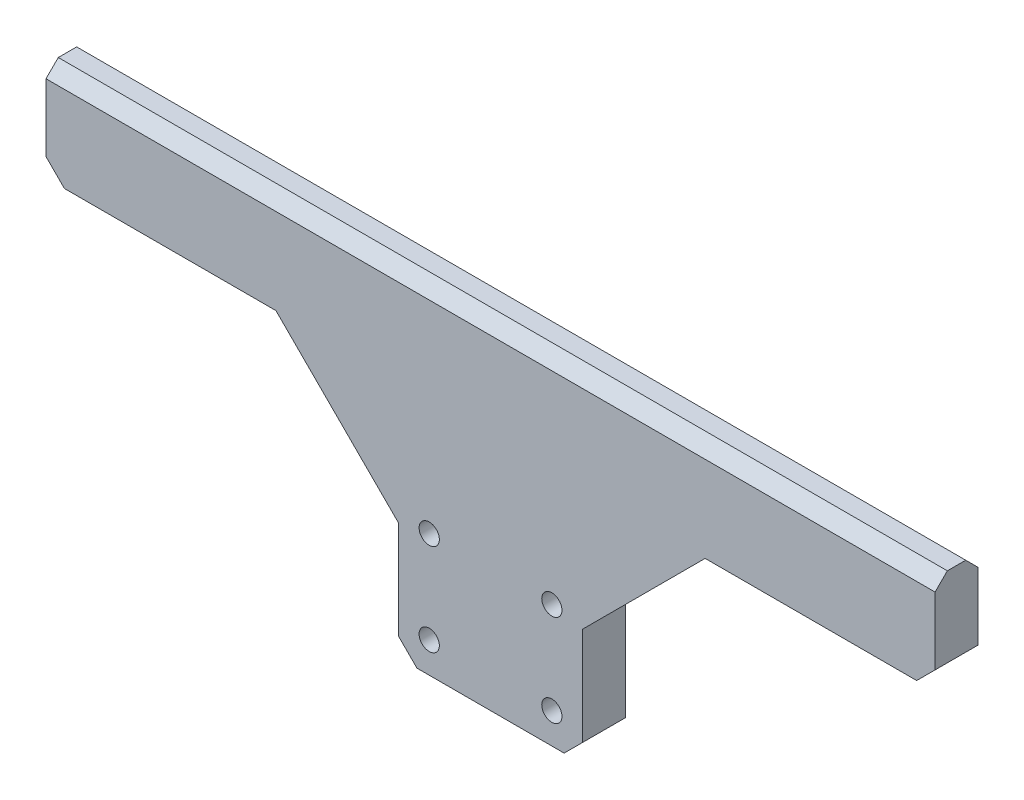
SolidWorks part; units mm, degrees
ref_plane "Front" through (0, 0, 0) normal (0, 0, 1) x (1, 0, 0)
ref_plane "Top" through (0, 0, 0) normal (0, 1, 0) x (1, 0, 0)
ref_plane "Right" through (0, 0, 0) normal (1, 0, 0) x (0, 0, -1)
sketch "Esquisse1" plane through (0, 0, 0) normal (0, 0, 1) x (1, 0, 0)
  line L1 (0, 0) -> (145, 0)
  line L2 (0, 0) -> (0, 25)
  line L3 (0, 25) -> (145, 25)
  line L4 (145, 0) -> (145, 25)
  dimension "D1" = 145
  dimension "D2" = 25
extrude "Boss.-Extru.1" add sketch "Esquisse1" along normal blind 7
sketch "Esquisse2" plane through (0, 0, 7) normal (0, 0, 1) x (1, 0, 0)
  line L0 (72.5, 0) -> (72.5, 25) construction
  line L1 (0, 0) -> (145, 0) construction
  line L2 (145, 25) -> (0, 25) construction
  line L3 (72.5, 12.5) -> (26.2893, 12.5) construction
  circle A0 centre (62.5, 20) radius 1.65
  circle A1 centre (62.5, 5) radius 1.65
  circle A2 centre (82.5, 5) radius 1.65
  circle A3 centre (82.5, 20) radius 1.65
  dimension "D1" = 20
  dimension "D2" = 15
  dimension "D3" = 3.3
extrude "Enlèv. mat.-Extru.1" cut sketch "Esquisse2" against normal through all both and the other way through all
sketch "Esquisse3" plane through (0, 0, 7) normal (0, 0, 1) x (1, 0, 0)
  line L0 (145, 0) -> (145, 25) construction
  line L1 (0, 25) -> (145, 25)
  line L2 (0, 25) -> (0, 55)
  line L3 (0, 55) -> (145, 55)
  line L4 (145, 25) -> (145, 55)
  dimension "D1" = 30
extrude "Boss.-Extru.2" add sketch "Esquisse3" against normal up to vertex (7 mm away) up to point (145, 25, 0)
chamfer "Chanfrein1" distance 2 angle 45 2 edges at (72.5, 55, 0) (72.5, 55, 7)
sketch "Esquisse4" plane through (0, 0, 7) normal (0, 0, 1) x (1, 0, 0)
  line L0 (72.5, 0) -> (72.5, 55) construction
  line L1 (0, 0) -> (57.5, 0)
  line L2 (0, 0) -> (0, 39)
  line L3 (0, 39) -> (57.5, 39)
  line L4 (57.5, 0) -> (57.5, 39)
  line L5 (0, 0) -> (145, 0) construction
  line L6 (0, 55) -> (145, 55) construction
  line L7 (87.5, 0) -> (87.5, 39)
  line L8 (145, 39) -> (87.5, 39)
  line L9 (145, 0) -> (145, 39)
  line L10 (145, 0) -> (87.5, 0)
  dimension "D1" = 30
  dimension "D2" = 16
extrude "Enlèv. mat.-Extru.2" cut sketch "Esquisse4" against normal through all both and the other way through all
chamfer "Chanfrein2" distance 20 angle 45 2 edges at (87.5, 39, 3.5) (57.5, 39, 3.5)
chamfer "Chanfrein3" distance 3 angle 45 4 edges at (145, 39, 3.5) (87.5, 0, 3.5) (0, 39, 3.5) (57.5, 0, 3.5)
